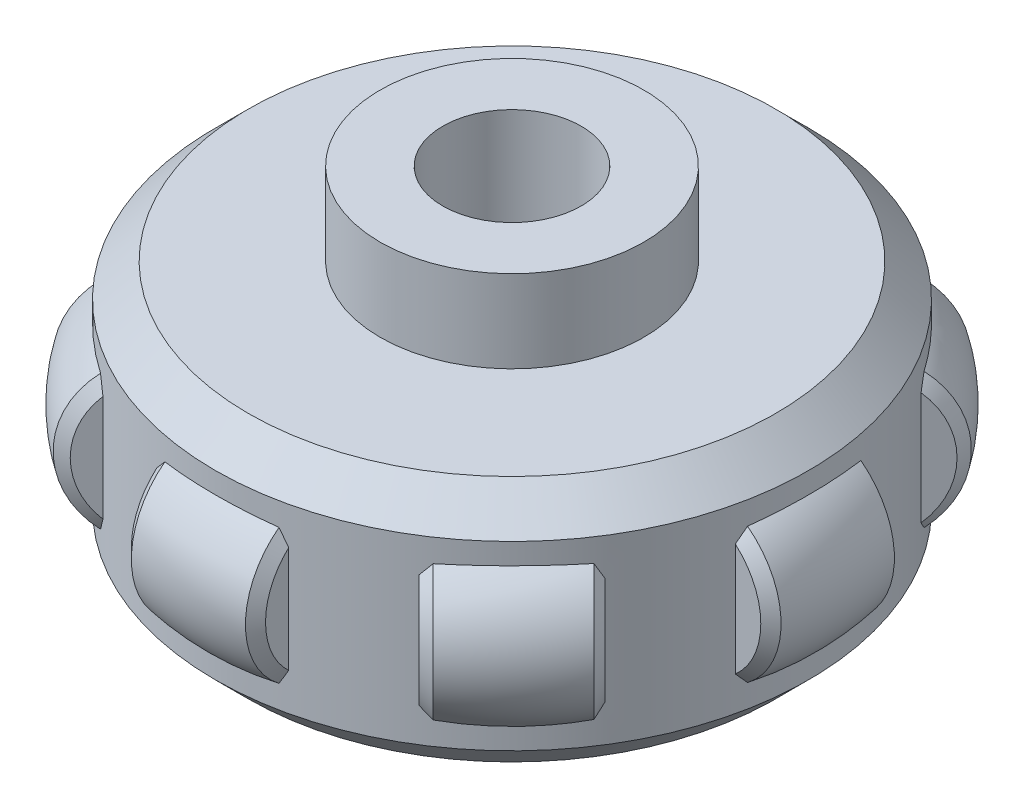
SolidWorks part; units mm, degrees
ref_plane "前视基准面" through (0, 0, 0) normal (0, 0, 1) x (1, 0, 0)
ref_plane "上视基准面" through (0, 0, 0) normal (0, 1, 0) x (1, 0, 0)
ref_plane "右视基准面" through (0, 0, 0) normal (1, 0, 0) x (0, 0, -1)
sketch "草图1" plane through (0, 0, 0) normal (0, 1, 0) x (1, 0, 0)
  circle A0 centre (0, 0) radius 18
  circle A1 centre (0, 0) radius 4.2
  dimension "D1" = 36
  dimension "D2" = 8.4
extrude "凸台-拉伸1" add sketch "草图1" along normal mid plane 15
sketch "草图2" plane through (0, 0, 0) normal (0, 1, 0) x (1, 0, 0)
  circle A0 centre (0, 0) radius 4.2
  circle A1 centre (0, 0) radius 8
  dimension "D1" = 16
extrude "凸台-拉伸2" add sketch "草图2" along normal mid plane 25
sketch "草图3" plane through (0, 0, 0) normal (0, 1, 0) x (1, 0, 0)
  line L0 (-4, 14.5458) -> (4, 14.5458)
  line L1 (0, 0) -> (0, 27.0801) construction
  line L2 (4, 14.5458) -> (4, 19.5959)
  line L3 (-4, 19.5959) -> (-4, 14.5458)
  arc A0 (4, 19.5959) -> (-4, 19.5959) centre (0, 0) ccw
  dimension "D1" = 20
  dimension "D2" = 8
revolve "旋转1" add sketch "草图3" angle 360 about L0
chamfer "倒角2" distance 0.5 angle 45 2 edges at (4, 0, -19.5959) (-4, 0, -19.5959) first distance on face at (4, 0, -18.5729) first distance on face at (0, 0, -18.7593)
pattern_circular "阵列(圆周)1" count 8 over 360 about axis through (0, 7.5, 0) along (0, -1, 0) of "旋转1", "倒角2"
chamfer "倒角1" distance 2 angle 45 2 edges at (0, -7.5, 18) (0, 7.5, 18)
